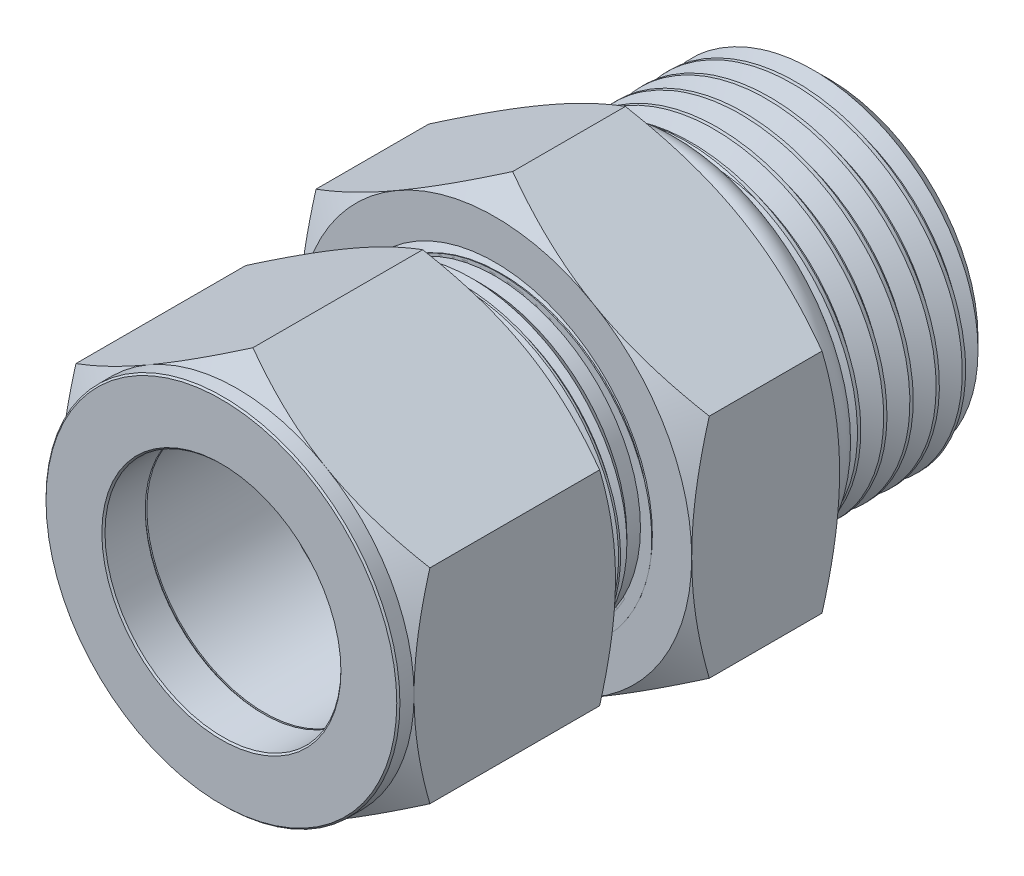
SolidWorks part; units mm, degrees
note: '?' marks a value the reader was unsure of.
ref_plane "Front Plane" through (0, 0, 0) normal (0, 0, 1) x (1, 0, 0)
ref_plane "Top Plane" through (0, 0, 0) normal (0, 1, 0) x (1, 0, 0)
ref_plane "Right Plane" through (0, 0, 0) normal (1, 0, 0) x (0, 0, -1)
sketch "Sketch1" plane through (0, 0, 0) normal (1, 0, 0) x (0, 0, -1)
  line L0 (0, 0) -> (49.022, 0) construction
  line L1 (0, 9.525) -> (0, -9.525) construction
  line L2 (17.526, 14.2875) -> (17.526, -14.2875) construction
  line L3 (7.0104, 12.7) -> (7.0104, -12.7) construction
  line L4 (7.0104, 12.7) -> (7.0104, 11.43) construction
  line L5 (34.036, 15.875) -> (34.036, -15.875) construction
  line L6 (6.1976, 11.8364) -> (13.5128, 10.0584) construction
  line L7 (13.5128, 10.0584) -> (13.5128, 9.525) construction
  line L8 (13.5128, 9.525) -> (7.3152, 9.525) construction
  line L9 (7.3152, 9.525) -> (6.1976, 10.6426) construction
  line L10 (6.1976, 10.6426) -> (6.1976, 11.8364) construction
  line L11 (3.5052, 11.0363) -> (4.7752, 11.0363) construction
  line L12 (4.7752, 11.0363) -> (4.7752, 10.6426) construction
  line L13 (4.7752, 10.6426) -> (6.1976, 10.6426) construction
  line L14 (34.036, 7.9375) -> (34.036, -7.9375) construction
  line L15 (6.1976, 10.6426) -> (6.1976, 9.525) construction
  line L16 (7.3152, 9.525) -> (3.5052, 9.525) construction
  line L17 (3.5052, 9.525) -> (3.5052, 11.0363) construction
  line L18 (6.1976, 9.525) -> (7.3152, 9.525) construction
  line L19 (0, 9.525) -> (3.5052, 9.525) construction
  line L20 (3.5052, 9.525) -> (7.0104, 9.525) construction
  line L21 (49.022, 13.4937) -> (49.022, -13.4937) construction
  line L22 (34.036, 13.4937) -> (34.036, -13.4937) construction
  line L23 (34.036, 13.4937) -> (49.022, 13.4937) construction
  line L24 (34.036, 13.4937) -> (34.036, 11.3771) construction
  line L25 (35.5092, 14.6812) -> (35.5092, 11.7348) construction
  line L26 (49.022, 3.4163) -> (49.022, -3.4163) construction
  circle A0 centre (35.5092, 13.208) radius 1.4732 construction
  point P4 (1.778, 0)
  point P10 (7.0104, 0)
  point P12 (17.526, 0)
  point P15 (22.098, 0)
  point P16 (10.16, 0)
  point P17 (24.384, 0)
  point P40 (34.036, 0)
  dimension "R" = 14.986
sketch "Sketch2" plane through (0, 0, 0) normal (0, 0, 1) x (1, 0, 0)
  line L0 (0, 9.525) -> (0, -9.525) construction
  line L1 (0, 16.4978) -> (-14.2875, 8.2489)
  line L2 (-14.2875, 8.2489) -> (-14.2875, -8.2489)
  line L3 (-14.2875, -8.2489) -> (0, -16.4978)
  line L4 (0, -16.4978) -> (14.2875, -8.2489)
  line L5 (14.2875, -8.2489) -> (14.2875, 8.2489)
  line L6 (14.2875, 8.2489) -> (0, 16.4978)
  line L7 (0, 16.4978) -> (0, 0) construction
  circle A0 centre (0, 0) radius 14.2875 construction
extrude "Boss-Extrude1" add sketch "Sketch2" against normal up to vertex (17.526 mm away) up to point (0, 0, -17.526)
sketch "Sketch3" plane through (0, 0, 0) normal (1, 0, 0) x (0, 0, -1)
  line L0 (0, 16.4978) -> (0, 14.2875)
  line L1 (0, 8.2489) -> (0, 16.4978) construction
  line L2 (0, 14.2875) -> (1.27, 14.2875)
  line L3 (1.27, 14.2875) -> (2.5461, 16.4978)
  line L4 (17.526, 16.4978) -> (0, 16.4978) construction
  line L5 (2.5461, 16.4978) -> (16.2499, 16.4978)
  line L6 (16.2499, 16.4978) -> (17.526, 14.2875)
  line L7 (17.526, 14.2875) -> (17.526, 16.4978)
  line L8 (17.526, 16.4978) -> (17.526, 18.7081)
  line L9 (17.526, 18.7081) -> (0, 18.7081)
  line L10 (0, 18.7081) -> (0, 16.4978)
  line L11 (0, 9.525) -> (0, 0)
  line L12 (0, 9.525) -> (0, -9.525) construction
  line L13 (0, 0) -> (17.526, 0)
  line L14 (17.526, 14.2875) -> (17.526, -14.2875) construction
  line L15 (17.526, 0) -> (17.526, 12.7)
  line L16 (17.526, 12.7) -> (7.0104, 12.7)
  line L17 (7.0104, 12.7) -> (7.0104, 11.43) construction
  line L18 (7.0104, 11.43) -> (3.5052, 11.43) construction
  line L19 (3.5052, 11.43) -> (3.5052, 9.525)
  line L20 (3.5052, 9.525) -> (0, 9.525)
  line L21 (3.5052, 11.43) -> (3.5052, 12.7) construction
  line L22 (3.5052, 12.7) -> (7.0104, 12.7) construction
  line L23 (7.0104, 12.065) -> (3.5052, 12.065)
  line L24 (3.5052, 12.065) -> (3.5052, 11.43)
  line L25 (7.0104, 12.065) -> (7.0104, 12.7)
  dimension "D1" = 30
  dimension "D2" = 1.27
revolve "Cut-Revolve1" cut sketch "Sketch3" angle 360 about L0
chamfer "Chamfer1" distance 0.127 angle 45 3 edges at (9.525, 0, -3.5052) (9.525, 0, 0) (14.2875, 0, 0)
sketch "Sketch4" plane through (0, 0, 0) normal (1, 0, 0) x (0, 0, -1)
  line L1 (34.036, 0) -> (10.16, 0)
  line L2 (34.036, 0) -> (34.036, 12.7)
  line L3 (34.036, 12.7) -> (10.16, 12.7)
  line L4 (10.16, 0) -> (10.16, 12.7)
  dimension "D1" = 23.876
revolve "Revolve1" add sketch "Sketch4" angle 360 about L1
sketch "Sketch7" plane through (0, 0, -34.036) normal (0, 0, -1) x (-1, 0, 0)
  line L0 (0, 0) -> (0, 18.3309) construction
  line L1 (0, 18.3309) -> (-15.875, 9.1654)
  line L2 (-15.875, 9.1654) -> (-15.875, -9.1654)
  line L3 (-15.875, -9.1654) -> (0, -18.3309)
  line L4 (0, -18.3309) -> (15.875, -9.1654)
  line L5 (15.875, -9.1654) -> (15.875, 9.1654)
  line L6 (15.875, 9.1654) -> (0, 18.3309)
  circle A0 centre (0, 0) radius 15.875 construction
extrude "Boss-Extrude2" add sketch "Sketch7" against normal up to vertex (11.938 mm away) separate body up to point (0, 0, -22.098)
sketch "Sketch9" plane through (0, 0, 0) normal (1, 0, 0) x (0, 0, -1)
  line L0 (6.1976, 11.8364) -> (6.1976, 10.6426)
  line L1 (6.1976, 10.6426) -> (7.3152, 9.525)
  line L2 (7.3152, 9.525) -> (13.5128, 9.525)
  line L3 (13.5128, 9.525) -> (13.5128, 10.0584)
  line L4 (13.5128, 10.0584) -> (6.1976, 11.8364)
revolve "Revolve2" add sketch "Sketch9" angle 360 about L0
sketch "Sketch10" plane through (0, 0, 0) normal (1, 0, 0) x (0, 0, -1)
  line L0 (3.5052, 11.0363) -> (4.7752, 11.0363)
  line L1 (4.7752, 11.0363) -> (4.7752, 10.6426)
  line L2 (4.7752, 10.6426) -> (6.1976, 10.6426)
  line L4 (6.1976, 10.6426) -> (7.3152, 9.525)
  line L5 (7.3152, 9.525) -> (3.5052, 9.525)
  line L6 (3.5052, 9.525) -> (3.5052, 11.0363)
revolve "Revolve3" add sketch "Sketch10" angle 360 about L0
sketch "Sketch11" plane through (0, 0, 0) normal (1, 0, 0) x (0, 0, -1)
  line L0 (34.036, 0) -> (49.022, 0)
  line L1 (49.022, 0) -> (49.022, 13.4937)
  line L2 (49.022, 13.4937) -> (34.036, 13.4937)
  line L3 (34.036, 13.4937) -> (34.036, 0)
revolve "Revolve4" add sketch "Sketch11" angle 360 about L0
sketch "Sketch15" plane through (0, 0, 0) normal (1, 0, 0) x (0, 0, -1)
  line L0 (0, 0) -> (35.5092, 0) construction
  circle A0 centre (35.5092, 13.208) radius 1.4732 construction
  circle A1 centre (35.5092, 13.208) radius 1.4732
  point P3 (35.5092, 14.6812)
  point P7 (35.5092, -14.6812)
revolve "Revolve5" add sketch "Sketch15" angle 360 about L0
sketch "Sketch17" plane through (0, 0, -34.036) normal (0, 0, -1) x (-1, 0, 0)
  line L1 (15.875, 9.1654) -> (0, 18.3309) construction
  line L2 (0, 18.3309) -> (-15.875, 9.1654) construction
  line L3 (-15.875, 9.1654) -> (-15.875, -9.1654) construction
  line L4 (-15.875, -9.1654) -> (0, -18.3309) construction
  line L5 (0, -18.3309) -> (15.875, -9.1654) construction
  line L6 (15.875, -9.1654) -> (15.875, 9.1654) construction
  circle A0 centre (0, 0) radius 15.875
extrude "Cut-Extrude1" cut sketch "Sketch17" against normal through all draft 60 flip side to cut
sketch "Sketch18" plane through (0, 0, -22.098) normal (0, 0, 1) x (1, 0, 0)
  circle A0 centre (0, 0) radius 15.875 construction
  circle A1 centre (0, 0) radius 15.875
extrude "Cut-Extrude2" cut sketch "Sketch18" against normal through all draft 60 flip side to cut
sketch "Sketch16" plane through (0, 0, 0) normal (1, 0, 0) x (0, 0, -1)
  line L0 (49.022, 0) -> (10.16, 0)
  line L1 (0, 0) -> (49.022, 0) construction
  line L2 (10.16, 0) -> (10.16, 10.8733)
  line L3 (6.1976, 11.8364) -> (13.5128, 10.0584) construction
  line L4 (10.16, 10.8733) -> (15.7074, 9.525)
  line L5 (15.7074, 9.525) -> (24.384, 9.525)
  line L6 (24.384, 9.525) -> (24.384, 7.9375)
  line L7 (24.384, 7.9375) -> (49.022, 7.9375)
  line L8 (49.022, 13.4937) -> (49.022, -13.4937) construction
  line L9 (49.022, 7.9375) -> (49.022, 0) construction
  line L10 (13.5128, 9.525) -> (7.3152, 9.525) construction
  line L11 (49.022, 7.9375) -> (50.6095, 7.9375)
  line L12 (50.6095, 7.9375) -> (50.6095, 0)
  line L13 (50.6095, 0) -> (49.022, 0)
  dimension "D1" = 1.5875
revolve "Cut-Revolve5" cut sketch "Sketch16" angle 360 about L0
combine bodies "Combine3" operation type add bodies to combine 106 115 114
chamfer "Chamfer2" distance 1.4287 angle 45 1 edges at (13.4937, 0, -49.022)
sketch "Sketch5" plane through (0, 0, -10.16) normal (0, 0, -1) x (-1, 0, 0)
  circle A0 centre (0, 0) radius 12.7 construction
  circle A1 centre (0, 0) radius 12.7
  point P3 (0, 12.7)
curve "Helix/Spiral1" pitch 1.27 height 25.146 radius 12.7 centre (0, 0, -10.16) axis (0, 0, -1) start towards (0, 1, 0)
sketch "Sketch6" plane through (0, 0, 0) normal (1, 0, 0) x (0, 0, -1)
  line L0 (8.9694, 12.8375) -> (10.2394, 12.8375) construction
  line L1 (10.2394, 12.8375) -> (9.6044, 11.7376) construction
  line L2 (9.6044, 11.7376) -> (8.9694, 12.8375) construction
  line L3 (9.525, 11.8751) -> (9.6837, 11.8751) construction
  line L4 (9.0487, 12.7) -> (10.16, 12.7) construction
  line L5 (9.6044, 11.7376) -> (9.6044, 11.8751) construction
  line L6 (9.6044, 12.7) -> (9.6044, 12.8375) construction
  line L7 (9.525, 11.8751) -> (9.0091, 12.7687)
  line L8 (9.0091, 12.7687) -> (10.1997, 12.7687)
  line L9 (10.1997, 12.7687) -> (9.6837, 11.8751)
  line L10 (9.6837, 11.8751) -> (9.525, 11.8751)
  point P10 (9.6044, 12.7687)
  dimension "D1" = 1.27
  dimension "D2" = 0.1588
sweep "Cut-Sweep1" cut profiles "Sketch6" path "Helix/Spiral1" align with end faces yes
sketch "Sketch8" plane through (0, 0, 0) normal (1, 0, 0) x (0, 0, -1)
  line L0 (10.16, 12.8375) -> (10.16, 11.7376)
  line L1 (10.16, 11.7376) -> (11.2599, 12.8375)
  line L2 (11.2599, 12.8375) -> (10.16, 12.8375)
  line L3 (22.098, 12.8375) -> (19.8983, 12.8375)
  line L4 (19.8983, 12.8375) -> (20.9981, 11.7376)
  line L5 (20.9981, 11.7376) -> (22.098, 11.7376)
  line L6 (22.098, 11.7376) -> (22.098, 12.8375)
  line L7 (22.098, 15.875) -> (23.5159, 18.3309) construction
  line L8 (22.098, 18.3309) -> (22.098, 9.1654) construction
  line L9 (23.5159, 18.3309) -> (32.6181, 18.3309) construction
  line L10 (23.5159, 18.3309) -> (32.6181, 18.3309) construction
  line L11 (24.384, 7.9375) -> (34.036, 7.9375) construction
  line L12 (32.6181, 18.3309) -> (34.036, 15.875) construction
  line L14 (34.036, 18.3309) -> (34.036, 20.7867) construction
  line L15 (34.036, 20.7867) -> (22.098, 20.7867) construction
  line L16 (22.098, 20.7867) -> (22.098, 18.3309) construction
  line L17 (22.098, 18.3309) -> (22.098, 15.875) construction
  line L18 (9.6044, 11.7376) -> (10.16, 11.7376) construction
  line L19 (10.2394, 12.8375) -> (10.16, 12.8375) construction
  line L20 (11.2599, 12.8375) -> (19.8983, 12.8375) construction
  line L21 (20.9981, 11.7376) -> (10.16, 11.7376) construction
  line L22 (10.16, 10.8733) -> (15.7074, 9.525) construction
  line L23 (34.036, 15.875) -> (34.036, 18.3309) construction
  line L24 (10.16, 8.9803) -> (10.16, -11.8798) construction
  line L25 (6.1976, 11.8364) -> (13.5128, 10.0584) construction
  line L26 (34.036, 0) -> (10.16, 0) construction
  line L27 (10.16, 0) -> (10.16, 10.8733) construction
  line L28 (15.7074, 9.525) -> (24.384, 9.525) construction
  line L29 (24.384, 9.525) -> (24.384, 7.9375) construction
  line L30 (34.036, 7.9375) -> (34.036, 0) construction
  line L31 (24.384, 0) -> (24.384, 7.9375) construction
  dimension "D1" = 30
revolve "Cut-Revolve2" cut sketch "Sketch8" angle 360 about L0
ref_plane "Plane2" through (0, 0, -50.292) normal (0, 0, -1) x (-1, 0, 0)
sketch "Sketch12" plane through (0, 0, -50.292) normal (0, 0, -1) x (-1, 0, 0)
  circle A0 centre (0, 0) radius 13.4937 construction
  circle A1 centre (0, 0) radius 12.065
  circle A2 centre (0, 0) radius 12.065
  point P0 (0, 13.4937)
  dimension "D1" = 0
curve "Helix/Spiral2" pitch 2.1167 height 17.1027 turns 8.08
sketch "Sketch13" plane through (0, 0, 0) normal (1, 0, 0) x (0, 0, -1)
  line L0 (50.1597, 13.7229) -> (52.2764, 13.7229) construction
  line L1 (50.1597, 13.7229) -> (51.218, 11.8898) construction
  line L2 (51.218, 11.8898) -> (52.2764, 13.7229) construction
  line L3 (51.0857, 12.1189) -> (51.3503, 12.1189) construction
  line L4 (50.292, 13.4937) -> (52.1441, 13.4937) construction
  line L5 (51.218, 11.8898) -> (51.218, 12.1189) construction
  line L6 (51.218, 13.4937) -> (51.218, 13.7229) construction
  line L7 (51.218, 13.6083) -> (52.2102, 13.6083) construction
  line L8 (51.218, 11.8898) -> (51.218, -13.4937) construction
  line L9 (51.218, -13.4937) -> (49.1014, -13.4937) construction
  line L10 (49.1014, -13.4937) -> (46.9847, -13.4937) construction
  line L11 (46.9847, -13.4937) -> (44.868, -13.4937) construction
  line L12 (50.1597, 13.7229) -> (52.2102, 13.6083)
  line L13 (52.2102, 13.6083) -> (51.3503, 12.1189)
  line L14 (51.3503, 12.1189) -> (51.0857, 12.1189)
  line L15 (51.0857, 12.1189) -> (50.1597, 13.7229)
  line L16 (34.036, -13.4937) -> (47.5932, -13.4937) construction
  line L17 (44.868, -13.4937) -> (42.7514, -13.4937) construction
  line L18 (42.7514, -13.4937) -> (40.6347, -13.4937) construction
  dimension "D1" = 2.1167
  dimension "D2" = 0.2646
sweep "Cut-Sweep2" cut profiles "Sketch13" path "Helix/Spiral2" align with end faces yes
ref_plane "Plane1" through (-6.5006, 11.8247, -35.0407) normal (-0.876, -0.4816, 0.0249) x (0.4788, -0.8623, 0.1649)
sketch "Sketch14" plane through (0, 0, 0) normal (1, 0, 0) x (0, 0, -1)
  line L0 (51.218, 11.8898) -> (49.022, 11.8898) construction
  line L1 (37.7022, 13.7229) -> (34.036, 13.7229)
  line L2 (49.022, 0) -> (34.036, 0) construction
  line L3 (49.022, 0) -> (49.022, 7.9375) construction
  line L4 (49.022, 7.9375) -> (34.036, 7.9375) construction
  line L5 (49.022, 13.4937) -> (49.022, -13.4937) construction
  line L6 (49.022, 11.8898) -> (47.1889, 13.7229) construction
  line L7 (47.1889, 13.7229) -> (49.022, 13.7229) construction
  line L8 (49.022, 13.7229) -> (49.022, 11.8898) construction
  line L9 (50.1597, 13.7229) -> (52.2764, 13.7229) construction
  line L10 (34.036, 0) -> (34.036, 7.9375) construction
  line L11 (34.036, 13.7229) -> (34.036, 11.8898)
  line L12 (34.036, 11.8898) -> (35.8691, 11.8898)
  line L13 (35.8691, 11.8898) -> (37.7022, 13.7229)
  line L14 (37.7022, 13.7229) -> (47.1889, 13.7229) construction
  line L15 (49.022, 11.8898) -> (35.8691, 11.8898) construction
  line L17 (34.036, 15.875) -> (34.036, -15.875) construction
revolve "Cut-Revolve4" cut sketch "Sketch14" angle 360 about L0
sketch "Sketch19" plane through (0, 0, 0) normal (1, 0, 0) x (0, 0, -1)
  line L5 (22.098, 13.7482) -> (22.098, 0) construction
  line L8 (22.098, 12.7) -> (34.036, 12.7)
  line L9 (22.098, 12.7) -> (22.098, 11.8751)
  line L10 (22.098, 11.8751) -> (34.036, 11.8751)
  line L11 (34.036, 12.7) -> (34.036, 11.8751)
  line L12 (34.036, 15.875) -> (34.036, -15.875) construction
revolve "Cut-Revolve7" cut sketch "Sketch19" angle 360 about L0
ref_axis "Center Axis 1" through (0, 0, -34.036) along (0, 0, -1)?
ref_plane "Contact Plane 1" through (0, 0, 0) normal (0, 0, 1) x (1, 0, 0)
ref_plane "Contact Plane 2" through (0, 0, -49.022) normal (0, 0, -1) x (-1, 0, 0)
equation "\"D4@Helix/Spiral1\" = \"Straight Thread Pitch@Sketch1\""
equation "\"D3@Helix/Spiral1\" = \"D4@Helix/Spiral1\" + \"D1@Sketch4\""
equation "\"D1@Sketch6\" = \"D4@Helix/Spiral1\""
equation "\"D2@Sketch6\" = \"D1@Sketch6\" / 8"
equation "\"D4@Helix/Spiral2\" = \"Thread Pitch@Sketch1\""
equation "\"D3@Helix/Spiral2\" = \"D4@Helix/Spiral2\" + \"R@Sketch1\""
equation "\"D1@Sketch13\" = \"D4@Helix/Spiral2\""
equation "\"D2@Sketch13\" = \"D1@Sketch13\" / 8"
